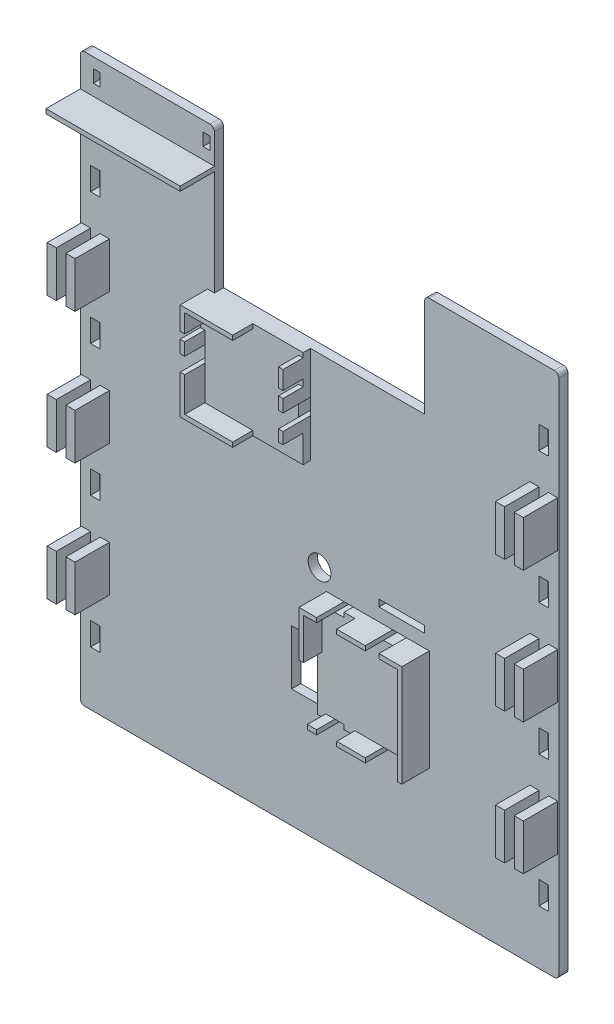
SolidWorks part; units mm, degrees
ref_plane "Front Plane" through (0, 0, 0) normal (0, 0, 1) x (1, 0, 0)
ref_plane "Top Plane" through (0, 0, 0) normal (0, 1, 0) x (1, 0, 0)
ref_plane "Right Plane" through (0, 0, 0) normal (1, 0, 0) x (0, 0, -1)
sketch "Sketch1" plane through (0, 0, 0) normal (0, 0, 1) x (1, 0, 0)
  line L1 (-100, -115) -> (100, -115)
  line L2 (-100, -115) -> (-100, 115)
  line L3 (-100, 115) -> (100, 115)
  line L4 (100, -115) -> (100, 115)
  line L5 (-100, -115) -> (100, 115) construction
  line L6 (-100, 115) -> (100, -115) construction
  point P0 (0, 0)
  dimension "D1" = 230
  dimension "D2" = 200
extrude "Boss-Extrude1" add sketch "Sketch1" along normal blind 70
sketch "Sketch2" plane through (0, 0, 70) normal (0, 0, 1) x (1, 0, 0)
  line L0 (100, 115) -> (-100, 115) construction
  line L1 (-96, -111) -> (96, -111)
  line L2 (-96, -111) -> (-96, 111)
  line L3 (-96, 111) -> (96, 111)
  line L4 (96, -111) -> (96, 111)
  line L5 (-96, -111) -> (96, 111) construction
  line L6 (-96, 111) -> (96, -111) construction
  line L7 (-100, 115) -> (-100, -115) construction
  point P0 (0, 0)
  dimension "D1" = 4
  dimension "D2" = 4
extrude "Cut-Extrude1" cut sketch "Sketch2" against normal blind 66
sketch "Sketch4" plane through (0, -115, 0) normal (0, -1, 0) x (1, 0, 0)
  line L0 (-100, 70) -> (-100, 0) construction
  line L1 (-98, 45) -> (98, 45)
  line L2 (-98, 45) -> (-98, 70)
  line L3 (-98, 70) -> (98, 70)
  line L4 (98, 45) -> (98, 70)
  line L5 (100, 70) -> (100, 0) construction
  line L6 (-100, 70) -> (100, 70) construction
  dimension "D1" = 2
  dimension "D2" = 2
  dimension "D3" = 0
  dimension "D4" = 25
extrude "Cut-Extrude3" cut sketch "Sketch4" against normal blind 10
sketch "Sketch10" plane through (0, 0, 4) normal (0, 0, 1) x (1, 0, 0)
  line L0 (-96, 111) -> (-96, -111) construction
  line L1 (-96, -111) -> (96, -111) construction
  circle A0 centre (0, -11) radius 5
  dimension "D1" = 10
  dimension "D2" = 96
  dimension "D3" = 100
extrude "Cut-Extrude8" cut sketch "Sketch10" against normal through all
sketch "Sketch11" plane through (0, 0, 70) normal (0, 0, 1) x (1, 0, 0)
  line L0 (-98, -105) -> (-98, -115) construction
  line L1 (-98, -105) -> (-100, -105)
  line L2 (-98, -105) -> (-98, -115)
  line L3 (-98, -115) -> (-100, -115)
  line L4 (-100, -105) -> (-100, -115)
  dimension "D1" = 10
extrude "Boss-Extrude2" add sketch "Sketch11" along normal blind 20
sketch "Sketch12" plane through (0, 0, 90) normal (0, 0, 1) x (1, 0, 0)
  line L0 (-100, -105) -> (-100, -115) construction
  line L1 (-100, -107.5) -> (-98, -107.5)
  line L2 (-100, -107.5) -> (-100, -112.5)
  line L3 (-100, -112.5) -> (-98, -112.5)
  line L4 (-98, -107.5) -> (-98, -112.5)
  line L5 (-98, -115) -> (-98, -105) construction
  line L6 (-98, -105) -> (-100, -105) construction
  dimension "D1" = 2.5
  dimension "D2" = 5
extrude "Cut-Extrude9" cut sketch "Sketch12" against normal blind 20
fillet "Fillet1" radius 2.5 2 edges at (-99, -112.5, 70) (-99, -107.5, 70)
sketch "Sketch13" plane through (0, 0, 70) normal (0, 0, 1) x (1, 0, 0)
  line L0 (98, -115) -> (100, -115) construction
  line L1 (98, -105) -> (100, -105)
  line L2 (98, -105) -> (98, -115)
  line L3 (98, -115) -> (100, -115)
  line L4 (100, -105) -> (100, -115)
  dimension "D1" = 0
  dimension "D2" = 2
extrude "Boss-Extrude3" add sketch "Sketch13" along normal blind 20
sketch "Sketch14" plane through (0, 0, 90) normal (0, 0, 1) x (1, 0, 0)
  line L0 (98, -105) -> (98, -115) construction
  line L1 (98, -107.5) -> (100, -107.5)
  line L2 (98, -107.5) -> (98, -112.5)
  line L3 (98, -112.5) -> (100, -112.5)
  line L4 (100, -107.5) -> (100, -112.5)
  line L5 (100, -115) -> (100, -105) construction
  line L6 (98, -105) -> (96, -105) construction
  dimension "D1" = 2.5
  dimension "D2" = 5
extrude "Cut-Extrude10" cut sketch "Sketch14" against normal blind 20
fillet "Fillet2" radius 2.5 2 edges at (99, -112.5, 70) (99, -107.5, 70)
sketch "Sketch15" plane through (0, 115, 0) normal (0, 1, 0) x (1, 0, 0)
  line L0 (100, -70) -> (-100, -70) construction
  line L1 (96, -70) -> (-96, -70)
  line L2 (96, -70) -> (96, -4)
  line L3 (96, -4) -> (-96, -4)
  line L4 (-96, -70) -> (-96, -4)
  line L5 (-100, -70) -> (-100, 0) construction
  line L6 (100, -70) -> (100, 0) construction
  line L7 (100, 0) -> (-100, 0) construction
  dimension "D1" = 4
  dimension "D2" = 4
  dimension "D3" = 4
extrude "Cut-Extrude11" cut sketch "Sketch15" against normal through all
sketch "Sketch16" plane through (-98, 0, 0) normal (1, 0, 0) x (0, 0, -1)
  line L0 (-90, -107.5) -> (-72.5, -107.5)
  line L1 (-72.5, -112.5) -> (-90, -112.5)
  line L2 (-90, -112.5) -> (-90, -115)
  line L3 (-90, -115) -> (-45, -115)
  line L4 (-45, -115) -> (-45, -105)
  line L5 (-45, -105) -> (-90, -105)
  line L6 (-90, -105) -> (-90, -107.5)
  arc A0 (-72.5, -107.5) -> (-72.5, -112.5) centre (-72.5, -110) cw
extrude "Boss-Extrude4" add sketch "Sketch16" along normal blind 2
sketch "Sketch18" plane through (100, 0, 0) normal (1, 0, 0) x (0, 0, -1)
  line L0 (-70, -105) -> (-70, 115) construction
  line L1 (-70, 115) -> (0, 115) construction
  circle A0 centre (-43, -35) radius 5
  dimension "D2" = 10
  dimension "D1" = 27
  dimension "D3" = 150
extrude "Cut-Extrude12" cut sketch "Sketch18" against normal through all
sketch "Sketch19" plane through (100, 0, 0) normal (1, 0, 0) x (0, 0, -1)
  line L0 (-90, -115) -> (0, -115) construction
  line L1 (0, -115) -> (0, 115) construction
  circle A0 centre (-15, -95) radius 5
  dimension "D1" = 10
  dimension "D2" = 20
  dimension "D3" = 15
extrude "Cut-Extrude13" cut sketch "Sketch19" against normal through all
sketch "Sketch20" plane through (100, 0, 0) normal (1, 0, 0) x (0, 0, -1)
  line L0 (-70, 115) -> (0, 115) construction
  line L1 (0, -115) -> (0, 115) construction
  circle A0 centre (-15, 95) radius 5
  dimension "D1" = 10
  dimension "D2" = 20
  dimension "D3" = 15
extrude "Cut-Extrude14" cut sketch "Sketch20" against normal through all
sketch "Sketch17" plane through (98, 0, 0) normal (-1, 0, 0) x (0, 0, 1)
  line L0 (90, -107.5) -> (72.5, -107.5)
  line L1 (72.5, -112.5) -> (90, -112.5)
  line L2 (90, -112.5) -> (90, -115)
  line L3 (90, -115) -> (45, -115)
  line L4 (45, -115) -> (45, -105)
  line L5 (45, -105) -> (90, -105)
  line L6 (90, -105) -> (90, -107.5)
  arc A0 (72.5, -107.5) -> (72.5, -112.5) centre (72.5, -110) ccw
extrude "Boss-Extrude5" add sketch "Sketch17" along normal blind 2
sketch "Sketch21" plane through (100, 0, 0) normal (1, 0, 0) x (0, 0, -1)
  line L1 (-90, -115) -> (-70, -115)
  line L2 (-90, -115) -> (-90, -105)
  line L3 (-90, -105) -> (-70, -105)
  line L4 (-70, -115) -> (-70, -105)
extrude "Cut-Extrude15" cut sketch "Sketch21" against normal through all
sketch "Sketch22" plane through (0, 0, 4) normal (0, 0, 1) x (1, 0, 0)
  line L0 (96, 115) -> (-96, 115) construction
  line L1 (46, 70) -> (-46, 70)
  line L2 (46, 70) -> (46, 115)
  line L3 (46, 115) -> (-46, 115)
  line L4 (-46, 70) -> (-46, 115)
  line L5 (96, -115) -> (96, 115) construction
  line L6 (-96, 115) -> (-96, -115) construction
  dimension "D1" = 50
  dimension "D2" = 50
  dimension "D3" = 45
extrude "Cut-Extrude16" cut sketch "Sketch22" against normal blind 10
sketch "Sketch24" plane through (100, 0, 0) normal (1, 0, 0) x (0, 0, -1)
  line L0 (-70, -115) -> (-70, 115) construction
  line L1 (-70, -115) -> (0, -115) construction
  circle A0 centre (-52.45, -102) radius 5.1
  dimension "D1" = 10.2
  dimension "D2" = 17.55
  dimension "D3" = 13
extrude "Cut-Extrude18" cut sketch "Sketch24" against normal through all
fillet "Fillet3" radius 20 1 edges at (98, -115, 70)
fillet "Fillet4" radius 20 1 edges at (-98, -115, 70)
sketch "Sketch31" plane through (0, 0, 70) normal (0, 0, 1) x (1, 0, 0)
  line L1 (100, 115) -> (96, 115)
  line L2 (100, 115) -> (100, -115)
  line L3 (100, -115) -> (96, -115)
  line L4 (96, 115) -> (96, -115)
extrude "Cut-Extrude24" cut sketch "Sketch31" against normal through all
sketch "Sketch33" plane through (96, 0, 0) normal (1, 0, 0) x (0, 0, -1)
  line L0 (-4, -115) -> (-4, 115) construction
  line L1 (-4, -67.5) -> (-19, -67.5)
  line L2 (-4, -67.5) -> (-4, -47.5)
  line L3 (-4, -47.5) -> (-19, -47.5)
  line L4 (-19, -67.5) -> (-19, -47.5)
  line L5 (-4, -115) -> (-50, -115) construction
  dimension "D1" = 20
  dimension "D2" = 15
  dimension "D3" = 47.5
extrude "Boss-Extrude7" add sketch "Sketch33" against normal blind 4
sketch "Sketch34" plane through (96, 0, 0) normal (1, 0, 0) x (0, 0, -1)
  line L0 (0, 115) -> (0, -115) construction
  line L1 (-4, -115) -> (0, -115)
  line L2 (-4, -115) -> (-4, -91.25)
  line L3 (-4, -91.25) -> (0, -91.25)
  line L4 (0, -115) -> (0, -91.25)
  dimension "D1" = 23.75
extrude "Boss-Extrude8" add sketch "Sketch34" along normal blind 4.2
sketch "Sketch35" plane through (96, 0, 0) normal (1, 0, 0) x (0, 0, -1)
  line L0 (-4, -91.25) -> (-4, -67.5) construction
  line L1 (-4, -81.25) -> (0, -81.25)
  line L2 (-4, -81.25) -> (-4, -33.75)
  line L3 (-4, -33.75) -> (0, -33.75)
  line L4 (0, -81.25) -> (0, -33.75)
  line L5 (0, 115) -> (0, -91.25) construction
  line L6 (0, -91.25) -> (-4, -91.25) construction
  point P10 (-2, -81.25)
  dimension "D1" = 10
  dimension "D2" = 47.5
extrude "Boss-Extrude9" add sketch "Sketch35" along normal blind 4.2
sketch "Sketch37" plane through (96, 0, 0) normal (1, 0, 0) x (0, 0, -1)
  line L0 (-4, -33.75) -> (-4, 115) construction
  line L1 (-4, -10) -> (-19, -10)
  line L2 (-4, -10) -> (-4, 10)
  line L3 (-4, 10) -> (-19, 10)
  line L4 (-19, -10) -> (-19, 10)
  line L5 (-4, -115) -> (0, -115) construction
  dimension "D1" = 20
  dimension "D2" = 15
  dimension "D3" = 105
extrude "Boss-Extrude10" add sketch "Sketch37" against normal blind 4
sketch "Sketch32" plane through (0, 0, 70) normal (0, 0, 1) x (1, 0, 0)
  line L1 (-96, 115) -> (-100, 115)
  line L2 (-96, 115) -> (-96, -115)
  line L3 (-96, -115) -> (-100, -115)
  line L4 (-100, 115) -> (-100, -115)
sketch "Sketch39" plane through (96, 0, 0) normal (1, 0, 0) x (0, 0, -1)
  line L0 (-4, -33.75) -> (-4, -10) construction
  line L1 (-4, -23.75) -> (0, -23.75)
  line L2 (-4, -23.75) -> (-4, 23.75)
  line L3 (-4, 23.75) -> (0, 23.75)
  line L4 (0, -23.75) -> (0, 23.75)
  line L5 (0, 115) -> (0, -33.75) construction
  line L6 (0, -33.75) -> (-4, -33.75) construction
  dimension "D1" = 10
  dimension "D2" = 47.5
extrude "Boss-Extrude11" add sketch "Sketch39" along normal blind 4.2
extrude "Cut-Extrude25" cut sketch "Sketch32" against normal through all
ref_plane "Plane2" through (0, 0, 0) normal (0, -1, 0) x (-1, 0, 0)
mirror "Mirror3" about plane through (0, 0, 0) normal (0, -1, 0) of "Boss-Extrude9"
mirror "Mirror5" about plane through (0, 0, 0) normal (0, -1, 0) of "Boss-Extrude7"
mirror "Mirror6" about plane through (0, 0, 0) normal (0, -1, 0) of "Boss-Extrude8"
sketch "Sketch40" plane through (100.2, 0, 0) normal (1, 0, 0) x (0, 0, -1)
  line L1 (-4, -115) -> (0, -115)
  line L2 (-4, -115) -> (-4, 115)
  line L3 (-4, 115) -> (0, 115)
  line L4 (0, -115) -> (0, 115)
extrude "Boss-Extrude12" add sketch "Sketch40" along normal blind 4.5
ref_plane "Plane3" through (98.1, 0, 0) normal (1, 0, 0) x (0, 0, -1)
mirror "Mirror8" about plane through (98.1, 0, 0) normal (1, 0, 0) of "Boss-Extrude10", "Mirror5", "Boss-Extrude7"
ref_plane "Plane4" through (0, 0, 0) normal (-1, 0, 0) x (0, 0, 1)
mirror "Mirror9" about plane through (0, 0, 0) normal (-1, 0, 0) of "Mirror8", "Boss-Extrude12", "Boss-Extrude10", "Boss-Extrude9", "Boss-Extrude8", "Boss-Extrude11", "Mirror3", "Mirror6", "Mirror5"
sketch "Sketch65" plane through (0, 0, 4) normal (0, 0, 1) x (1, 0, 0)
  line L0 (-46, 70) -> (46, 70) construction
  line L1 (-6, 29.5) -> (-47, 29.5)
  line L2 (-6, 29.5) -> (-6, 68)
  line L3 (-6, 68) -> (-47, 68)
  line L4 (-47, 29.5) -> (-47, 68)
  line L5 (-4, 27.5) -> (-49, 27.5)
  line L6 (-4, 27.5) -> (-4, 70)
  line L7 (-4, 70) -> (-49, 70)
  line L8 (-49, 27.5) -> (-49, 70)
  line L10 (-46, 115) -> (-46, 70) construction
  dimension "D1" = 41
  dimension "D2" = 38.5
  dimension "D3" = 2
  dimension "D4" = 2
  dimension "D5" = 2
  dimension "D6" = 2
  dimension "D7" = 0
  dimension "D8" = 40
extrude "Boss-Extrude23" add sketch "Sketch65" along normal blind 12
sketch "Sketch66" plane through (0, 0, 16) normal (0, 0, 1) x (1, 0, 0)
  line L0 (-4, 27.5) -> (-26, 27.5)
  line L1 (-49, 27.5) -> (-4, 27.5) construction
  line L2 (-26, 27.5) -> (-26, 29.5)
  line L3 (-47, 29.5) -> (-6, 29.5) construction
  line L4 (-26, 29.5) -> (-6, 29.5)
  line L5 (-6, 29.5) -> (-6, 39.5)
  line L6 (-6, 29.5) -> (-6, 68) construction
  line L7 (-6, 39.5) -> (-4, 39.5)
  line L8 (-4, 27.5) -> (-4, 70) construction
  line L9 (-4, 39.5) -> (-4, 27.5)
  dimension "D1" = 20
  dimension "D2" = 10
extrude "Cut-Extrude39" cut sketch "Sketch66" against normal blind 8.8
sketch "Sketch67" plane through (0, 0, 16) normal (0, 0, 1) x (1, 0, 0)
  line L0 (-6, 39.5) -> (-6, 68) construction
  line L1 (-6, 57) -> (-4, 57)
  line L2 (-6, 57) -> (-6, 60)
  line L3 (-6, 60) -> (-4, 60)
  line L4 (-4, 57) -> (-4, 60)
  line L5 (-4, 39.5) -> (-4, 70) construction
  line L6 (-6, 68) -> (-47, 68) construction
  point P8 (-5, 57)
  dimension "D1" = 11
  dimension "D2" = 8
extrude "Cut-Extrude40" cut sketch "Sketch67" against normal blind 8.8
sketch "Sketch68" plane through (0, 0, 16) normal (0, 0, 1) x (1, 0, 0)
  line L0 (-6, 68) -> (-47, 68) construction
  line L1 (-4, 70) -> (-26, 70)
  line L2 (-4, 70) -> (-4, 68)
  line L3 (-4, 68) -> (-26, 68)
  line L4 (-26, 70) -> (-26, 68)
  line L5 (-6, 60) -> (-6, 68) construction
  line L6 (-47, 68) -> (-47, 29.5) construction
  line L7 (-47, 57) -> (-49, 57)
  line L8 (-47, 57) -> (-47, 60)
  line L9 (-47, 60) -> (-49, 60)
  line L10 (-49, 57) -> (-49, 60)
  line L11 (-49, 70) -> (-49, 27.5) construction
  line L13 (-6, 68) -> (-47, 68) construction
  dimension "D1" = 20
  dimension "D2" = 3
  dimension "D3" = 8
extrude "Cut-Extrude41" cut sketch "Sketch68" against normal blind 8.8
sketch "Sketch69" plane through (0, 0, 16) normal (0, 0, 1) x (1, 0, 0)
  line L0 (-4, 39.5) -> (-4, 57) construction
  line L1 (-4, 44.5) -> (-6, 44.5)
  line L2 (-4, 44.5) -> (-4, 51.5)
  line L3 (-4, 51.5) -> (-6, 51.5)
  line L4 (-6, 44.5) -> (-6, 51.5)
  line L5 (-6, 29.5) -> (-6, 68) construction
  line L6 (-4, 39.5) -> (-6, 39.5) construction
  line L7 (-47, 68) -> (-47, 29.5) construction
  line L8 (-47, 44.5) -> (-49, 44.5)
  line L9 (-47, 44.5) -> (-47, 51.5)
  line L10 (-47, 51.5) -> (-49, 51.5)
  line L11 (-49, 44.5) -> (-49, 51.5)
  line L12 (-49, 70) -> (-49, 27.5) construction
  line L13 (-4, 39.5) -> (-6, 39.5) construction
  dimension "D1" = 7
  dimension "D2" = 5
  dimension "D3" = 7
  dimension "D4" = 5
extrude "Cut-Extrude42" cut sketch "Sketch69" against normal through all
sketch "Sketch70" plane through (0, 0, 4) normal (0, 0, 1) x (1, 0, 0)
  line L1 (-6, 29.5) -> (-47, 29.5)
  line L2 (-6, 29.5) -> (-6, 68)
  line L3 (-6, 68) -> (-47, 68)
  line L4 (-47, 29.5) -> (-47, 68)
extrude "Boss-Extrude24" add sketch "Sketch70" along normal blind 3.2
sketch "Sketch72" plane through (0, 115, 0) normal (0, 1, 0) x (1, 0, 0)
  line L1 (-46, -4) -> (-104.7, -4)
  line L2 (-46, -4) -> (-46, 0)
  line L3 (-46, 0) -> (-104.7, 0)
  line L4 (-104.7, -4) -> (-104.7, 0)
extrude "Boss-Extrude25" add sketch "Sketch72" along normal blind 18
sketch "Sketch73" plane through (0, 0, 4) normal (0, 0, 1) x (1, 0, 0)
  line L0 (-46, 133) -> (-46, 70) construction
  line L1 (-46, 116) -> (-104.7, 116)
  line L2 (-46, 116) -> (-46, 118)
  line L3 (-46, 118) -> (-104.7, 118)
  line L4 (-104.7, 116) -> (-104.7, 118)
  line L5 (-104.7, 133) -> (-104.7, -115) construction
  line L6 (104.7, 115) -> (46, 115) construction
  dimension "D1" = 1
  dimension "D2" = 2
extrude "Boss-Extrude26" add sketch "Sketch73" along normal blind 15
fillet "Fillet5" radius 2 6 edges at (104.7, 115, 2) (104.7, -115, 2) (-104.7, -115, 2) (-104.7, 133, 2) (-46, 133, 2) (46, 115, 2)
sketch "Sketch74" plane through (0, 0, 4) normal (0, 0, 1) x (1, 0, 0)
  line L0 (-46, 118) -> (-104.7, 118) construction
  line L1 (-96, 123) -> (-99, 123)
  line L2 (-96, 123) -> (-96, 128.5)
  line L3 (-96, 128.5) -> (-99, 128.5)
  line L4 (-99, 123) -> (-99, 128.5)
  line L5 (-51, 123) -> (-48, 123)
  line L6 (-51, 123) -> (-51, 128.5)
  line L7 (-51, 128.5) -> (-48, 128.5)
  line L8 (-48, 123) -> (-48, 128.5)
  line L9 (-46, 131) -> (-46, 118) construction
  point P10 (-49.5, 123)
  dimension "D1" = 5
  dimension "D2" = 3
  dimension "D3" = 5.5
  dimension "D4" = 5
  dimension "D5" = 3
  dimension "D6" = 5.5
  dimension "D7" = 45
  dimension "D8" = 2
extrude "Cut-Extrude43" cut sketch "Sketch74" against normal through all
sketch "Sketch75" plane through (0, 0, 4) normal (0, 0, 1) x (1, 0, 0)
  line L0 (-96, -23.75) -> (-96, -33.75) construction
  line L1 (48, -63.14) -> (3, -63.14)
  line L2 (48, -63.14) -> (48, -18.64)
  line L3 (48, -18.64) -> (3, -18.64)
  line L4 (3, -63.14) -> (3, -18.64)
  line L6 (102.7, -115) -> (-102.7, -115) construction
  dimension "D1" = 45
  dimension "D2" = 44.5
  dimension "D3" = 99
  dimension "D4" = 51.86
extrude "Boss-Extrude27" add sketch "Sketch75" along normal blind 4
sketch "Sketch76" plane through (0, 0, 8) normal (0, 0, 1) x (1, 0, 0)
  line L0 (48, -63.14) -> (48, -18.64)
  line L1 (48, -18.64) -> (19.5, -18.64)
  line L2 (48, -18.64) -> (3, -18.64) construction
  line L3 (19.5, -18.64) -> (19.5, -20.64)
  line L4 (19.5, -20.64) -> (46, -20.64)
  line L5 (46, -20.64) -> (46, -63.14)
  line L6 (3, -63.14) -> (48, -63.14) construction
  line L7 (46, -63.14) -> (48, -63.14)
  line L8 (13, -18.64) -> (13, -20.64)
  line L9 (13, -20.64) -> (5, -20.64)
  line L10 (5, -20.64) -> (5, -38.64)
  line L11 (5, -38.64) -> (3, -38.64)
  line L12 (3, -18.64) -> (3, -63.14) construction
  line L13 (3, -38.64) -> (3, -18.64)
  line L14 (3, -18.64) -> (13, -18.64)
  line L15 (38, -63.14) -> (38, -61.14)
  line L16 (38, -61.14) -> (19.5, -61.14)
  line L17 (19.5, -61.14) -> (19.5, -63.14)
  line L18 (19.5, -63.14) -> (38, -63.14)
  line L19 (14.7, -63.14) -> (6.7, -63.14)
  line L20 (6.7, -63.14) -> (6.7, -61.14)
  line L21 (14.7, -63.14) -> (14.7, -61.14)
  line L22 (14.7, -61.14) -> (6.7, -61.14)
  point P27 (14.7, -62.14)
  dimension "D1" = 2
  dimension "D2" = 2
  dimension "D3" = 2
  dimension "D4" = 2
  dimension "D5" = 2
  dimension "D6" = 2
  dimension "D7" = 6.5
  dimension "D8" = 20
  dimension "D9" = 18.5
  dimension "D10" = 8
  dimension "D11" = 4.8
  dimension "D12" = 8
  dimension "D13" = 0
extrude "Boss-Extrude28" add sketch "Sketch76" along normal blind 8
sketch "Sketch77" plane through (0, 0, 4) normal (0, 0, 1) x (1, 0, 0)
  line L0 (38, -61.14) -> (19.5, -61.14) construction
  line L1 (2.7734, -63.14) -> (-12.2266, -63.14)
  line L2 (2.7734, -63.14) -> (2.7734, -39.14)
  line L3 (2.7734, -39.14) -> (-12.2266, -39.14)
  line L4 (-12.2266, -63.14) -> (-12.2266, -39.14)
  dimension "D1" = 2
  dimension "D2" = 24
  dimension "D3" = 15
extrude "Cut-Extrude44" cut sketch "Sketch77" against normal through all
sketch "Sketch78" plane through (0, 0, 4) normal (0, 0, 1) x (1, 0, 0)
  line L0 (-4, 70) -> (46, 70) construction
  line L1 (46, -13) -> (26, -13)
  line L2 (46, -13) -> (46, -10)
  line L3 (46, -10) -> (26, -10)
  line L4 (26, -13) -> (26, -10)
  line L5 (46, 70) -> (46, 113) construction
  dimension "D1" = 80
  dimension "D2" = 3
  dimension "D3" = 20
  dimension "D4" = 0
extrude "Cut-Extrude45" cut sketch "Sketch78" against normal through all
sketch "Sketch79" plane through (0, 0, 16) normal (0, 0, 1) x (1, 0, 0)
  line L0 (19.5, -20.64) -> (46, -20.64) construction
  line L1 (38, -20.64) -> (32, -20.64)
  line L2 (38, -20.64) -> (38, -18.64)
  line L3 (38, -18.64) -> (32, -18.64)
  line L4 (32, -20.64) -> (32, -18.64)
  line L5 (48, -18.64) -> (19.5, -18.64) construction
  line L6 (19.5, -63.14) -> (38, -63.14) construction
  line L7 (32, -63.14) -> (38, -63.14)
  line L8 (32, -63.14) -> (32, -61.14)
  line L9 (32, -61.14) -> (38, -61.14)
  line L10 (38, -63.14) -> (38, -61.14)
  line L11 (6.7, -63.14) -> (14.7, -63.14) construction
  line L12 (14.7, -63.14) -> (10.7, -63.14)
  line L13 (14.7, -63.14) -> (14.7, -61.14)
  line L14 (14.7, -61.14) -> (10.7, -61.14)
  line L15 (10.7, -63.14) -> (10.7, -61.14)
  line L16 (14.7, -61.14) -> (6.7, -61.14) construction
  line L17 (5, -20.64) -> (13, -20.64) construction
  line L18 (10.7, -20.64) -> (14.7, -20.64)
  line L19 (10.7, -20.64) -> (10.7, -18.64)
  line L20 (10.7, -18.64) -> (14.7, -18.64)
  line L21 (14.7, -20.64) -> (14.7, -18.64)
  line L22 (14.7, -63.14) -> (14.7, -61.14) construction
  dimension "D1" = 6
  dimension "D2" = 0
  dimension "D3" = 6
  dimension "D4" = 4
  dimension "D5" = 0
  dimension "D6" = 4
  dimension "D7" = 0
extrude "Cut-Extrude46" cut sketch "Sketch79" against normal through all
